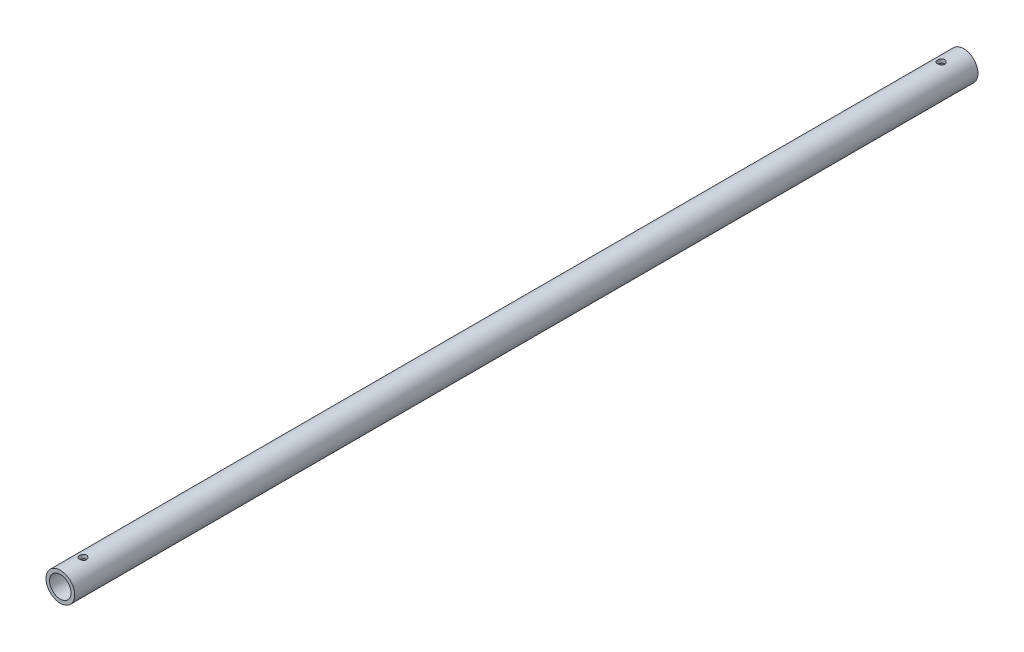
SolidWorks part; units mm, degrees
ref_plane "Front Plane" through (0, 0, 0) normal (0, 0, 1) x (1, 0, 0)
ref_plane "Top Plane" through (0, 0, 0) normal (0, 1, 0) x (1, 0, 0)
ref_plane "Right Plane" through (0, 0, 0) normal (1, 0, 0) x (0, 0, -1)
sketch "Sketch1" plane through (0, 0, 0) normal (0, 0, 1) x (1, 0, 0)
  circle A0 centre (0, 0) radius 6.35
  circle A1 centre (0, 0) radius 4.75
  dimension "D1" = 12.7
  dimension "D2" = 9.5
extrude "Boss-Extrude1" add sketch "Sketch1" along normal blind 400
sketch "Sketch2" plane through (0, 0, 0) normal (0, 1, 0) x (1, 0, 0)
  line L0 (4.75, 0) -> (-4.75, 0) construction
  line L1 (-6.35, -200) -> (6.35, -200)
  line L2 (-6.35, 0) -> (-6.35, -400) construction
  line L3 (6.35, -400) -> (6.35, 0) construction
  circle A0 centre (0, -10) radius 1.6
  circle A1 centre (0, -390) radius 1.6
  dimension "D1" = 3.2
  dimension "D2" = 10
extrude "Cut-Extrude1" cut sketch "Sketch2" against normal blind 400 and the other way blind 400 contours A0 | A1
